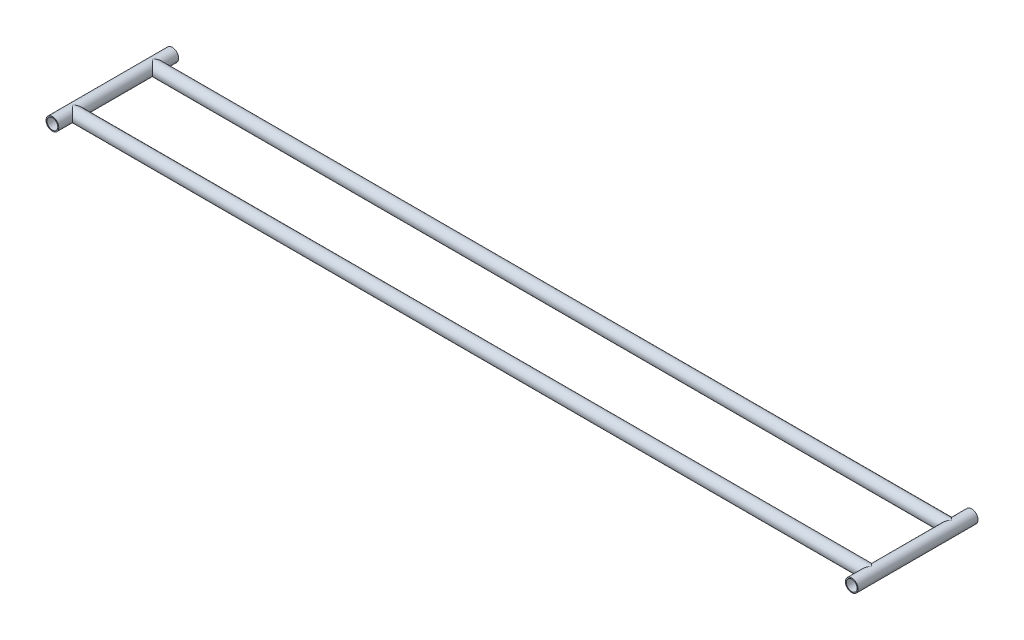
SolidWorks part; units mm, degrees
material "PVC Rigid"
ref_plane "Front Plane" through (0, 0, 0) normal (0, 0, 1) x (1, 0, 0)
ref_plane "Top Plane" through (0, 0, 0) normal (0, 1, 0) x (1, 0, 0)
ref_plane "Right Plane" through (0, 0, 0) normal (1, 0, 0) x (0, 0, -1)
sketch "Sketch1" plane through (0, 0, 0) normal (1, 0, 0) x (0, 0, -1)
  line L0 (-71.0406, 0) -> (82.5769, 0) construction
  circle A0 centre (-50, 0) radius 8
  circle A1 centre (-50, 0) radius 6.75
  circle A2 centre (50, 0) radius 6.75
  circle A3 centre (50, 0) radius 8
  dimension "D1" = 16
  dimension "D2" = 13.5
  dimension "D3" = 13.5
  dimension "D4" = 16
  dimension "D5" = 50
  dimension "D6" = 50
extrude "Boss-Extrude1" add sketch "Sketch1" along normal blind 1000
sketch "Sketch2" plane through (0, 0, 0) normal (0, 0, 1) x (1, 0, 0)
  circle A0 centre (0, 0) radius 8
  circle A1 centre (0, 0) radius 6.75
  dimension "D1" = 13.5
  dimension "D2" = 16
extrude "Boss-Extrude2" add sketch "Sketch2" along normal blind 75 and the other way blind 75
sketch "Sketch3" plane through (0, 0, 75) normal (0, 0, 1) x (1, 0, 0)
  circle A0 centre (0, 0) radius 6.75
  dimension "D1" = 13.5
extrude "Cut-Extrude1" cut sketch "Sketch3" against normal blind 150
sketch "Sketch4" plane through (0, 0, 0) normal (0, 0, 1) x (1, 0, 0)
  line L0 (1000, -8) -> (1000, 8) construction
  circle A0 centre (1000, 0) radius 8
  circle A1 centre (1000, 0) radius 6.75
  dimension "D1" = 16
  dimension "D2" = 13.5
extrude "Boss-Extrude3" add sketch "Sketch4" along normal blind 75 and the other way blind 75
sketch "Sketch6" plane through (0, 0, 75) normal (0, 0, 1) x (1, 0, 0)
  line L0 (1000, -6.75) -> (1000, 6.75) construction
  circle A0 centre (1000, 0) radius 6.75
  dimension "D1" = 13.5
extrude "Cut-Extrude2" cut sketch "Sketch6" against normal blind 150
